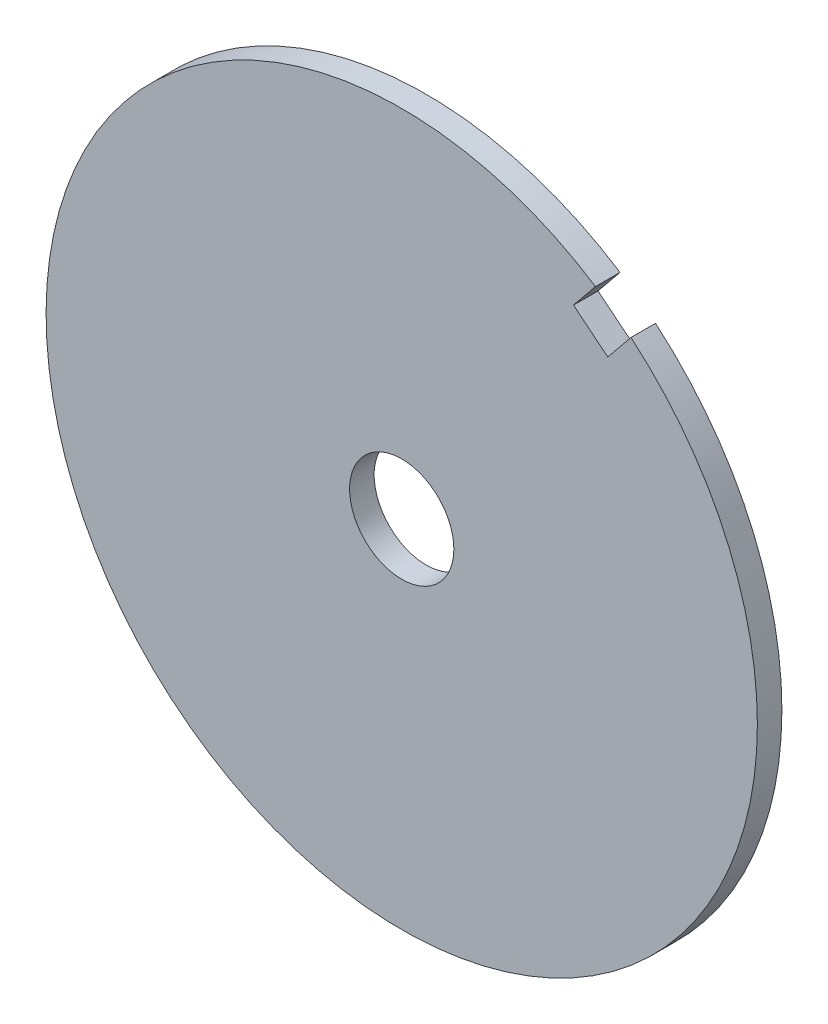
SolidWorks part; units mm, degrees
ref_plane "Front Plane" through (0, 0, 0) normal (0, 0, 1) x (1, 0, 0)
ref_plane "Top Plane" through (0, 0, 0) normal (0, 1, 0) x (1, 0, 0)
ref_plane "Right Plane" through (0, 0, 0) normal (1, 0, 0) x (0, 0, -1)
sketch "Sketch1" plane through (0, 0, 3372.7778) normal (0, 0, 1) x (1, 0, 0)
  circle A0 centre (0, 0) radius 92.075
  dimension "D1" = 184.15
extrude "Boss-Extrude1" add sketch "Sketch1" along normal blind 6.35
sketch "Sketch2" plane through (0, 0, 3379.1278) normal (0, 0, 1) x (1, 0, 0)
  circle A0 centre (0, 0) radius 13.4938
  dimension "D1" = 26.9875
extrude "Cut-Extrude1" cut sketch "Sketch2" against normal up to next
sketch "Sketch3" plane through (0, 0, 3379.1278) normal (0, 0, 1) x (1, 0, 0)
  line L0 (50.1638, 77.2101) -> (44.4747, 70.2165)
  line L1 (44.4747, 70.2165) -> (53.3415, 63.0036)
  line L2 (53.3415, 63.0036) -> (59.3522, 70.3926)
  line L3 (141.5029, 185.4682) -> (69.8687, 97.4083) construction
  line L4 (74.7947, 93.4011) -> (146.4289, 181.461) construction
  circle A0 centre (0, 0) radius 92.075 construction
  dimension "D1" = 2.54
  dimension "D2" = 2.54
  dimension "D3" = 9.525
extrude "Cut-Extrude2" cut sketch "Sketch3" against normal through all and the other way through all
